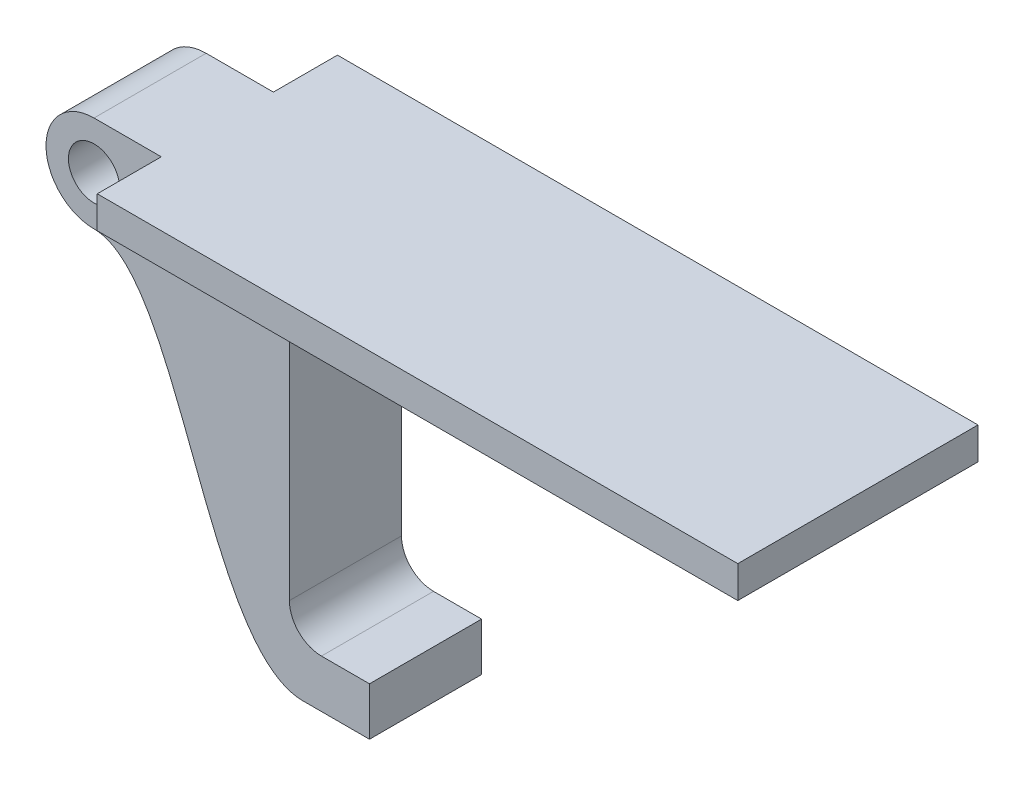
SolidWorks part; units mm, degrees
ref_plane "Ebene vorne" through (0, 0, 0) normal (0, 0, 1) x (1, 0, 0)
ref_plane "Ebene oben" through (0, 0, 0) normal (0, 1, 0) x (1, 0, 0)
ref_plane "Ebene rechts" through (0, 0, 0) normal (1, 0, 0) x (0, 0, -1)
sketch "Sketch1" plane through (0, 0, 0) normal (0, 1, 0) x (1, 0, 0)
  line L0 (-20, -7.5) -> (-20, -3.5)
  line L1 (-20, -7.5) -> (20, -7.5)
  line L2 (-20, 7.5) -> (20, 7.5)
  line L3 (20, -7.5) -> (20, 7.5)
  line L4 (-20, -7.5) -> (20, 7.5) construction
  line L5 (-20, 7.5) -> (20, -7.5) construction
  line L6 (-20, 3.5) -> (-20, 7.5)
  line L7 (-20, -3.5) -> (-27.2, -3.5)
  line L9 (-20, 3.5) -> (-27.2, 3.5)
  line L10 (-27.2, -3.5) -> (-27.2, 3.5)
  point P1 (0, 0)
  dimension "D1" = 15
  dimension "D2" = 40
  dimension "D3" = 7.2
  dimension "D4" = 7
extrude "Boss-Extrude1" add sketch "Sketch1" along normal blind 2
sketch "Sketch16" plane through (0, 0, 0) normal (0, -1, 0) x (1, 0, 0)
  line L1 (-20, 3.5) -> (-27.2, 3.5)
  line L2 (-20, 3.5) -> (-20, -3.5)
  line L3 (-20, -3.5) -> (-27.2, -3.5)
  line L4 (-27.2, 3.5) -> (-27.2, -3.5)
extrude "Boss-Extrude3" add sketch "Sketch16" along normal blind 4
sketch "Sketch17" plane through (0, 0, -3.5) normal (0, 0, -1) x (-1, 0, 0)
  line L0 (20, 2) -> (27.2, 2) construction
  line L1 (27.2, 2) -> (27.2, -4) construction
  circle A0 centre (24.2, -1) radius 1.6
  dimension "D1" = 3.2
  dimension "D2" = 3
  dimension "D3" = 3
extrude "Cut-Extrude4" cut sketch "Sketch17" against normal up to next
fillet "Fillet4" radius 3 2 edges at (-27.2, -4, 0) (-27.2, 2, 0)
sketch "Sketch18" plane through (0, 0, -3.5) normal (0, 0, -1) x (-1, 0, 0)
  line L1 (12, -18) -> (12, 0)
  line L2 (-20, 0) -> (20, 0) construction
  line L3 (12, 0) -> (20, 0)
  line L5 (7, -23) -> (10.9538, -23)
  line L6 (7, -23) -> (7, -20)
  line L7 (7, -20) -> (10, -20)
  line L10 (26.8692, -4) -> (21.5308, -4) construction
  line L11 (20, 0) -> (20, -4)
  line L12 (20, -4) -> (24.2, -4)
  arc A0 (10, -20) -> (12, -18) centre (10, -18) ccw
  spline S0 degree 3 poles (10.9538, -23) (17.1985, -23.3595) (18.7064, -4) (24.2, -4) knots 0 0 0 0 1 1 1 1
  point P15 (12, -20)
  dimension "D3" = 2
  dimension "D1" = 20
  dimension "D2" = 3
  dimension "D4" = 5
  dimension "D5" = 8
extrude "Boss-Extrude4" add sketch "Sketch18" against normal up to surface (7 mm away) up to face at (-25.8, -1, 3.5)
sketch "Sketch15" plane through (0, 0, 0) normal (0, -1, 0) x (1, 0, 0)
  line L0 (-4, 0) -> (-2, 0) construction
  line L1 (-4, 3.5) -> (-2, 3.5)
  line L2 (-4, -3.5) -> (-2, -3.5)
  line L7 (-7, 3.5) -> (-10.9538, 3.5)
  line L8 (-10.9538, 3.5) -> (-10.9538, -3.5)
  line L9 (-10.9538, -3.5) -> (-7, -3.5)
  line L10 (-7, -3.5) -> (-7, 3.5)
  line L11 (-7, 3.5) -> (-10.9538, 3.5) construction
  line L12 (-10.9538, 3.5) -> (-10.9538, -3.5) construction
  line L13 (-10.9538, -3.5) -> (-7, -3.5) construction
  line L14 (-7, -3.5) -> (-7, 3.5) construction
  arc A0 (-4, 3.5) -> (-4, -3.5) centre (-4, 0) ccw
  arc A1 (-2, -3.5) -> (-2, 3.5) centre (-2, 0) ccw
  point P3 (-3, 0)
  point P8 (-3.6545, 0)
  point P11 (0, 0)
  dimension "D1" = 7
  dimension "D2" = 2
  dimension "D3" = 0
  dimension "D4" = 4
extrude "Cut-Extrude3" [suppressed] cut sketch "Sketch15" against normal up to next
